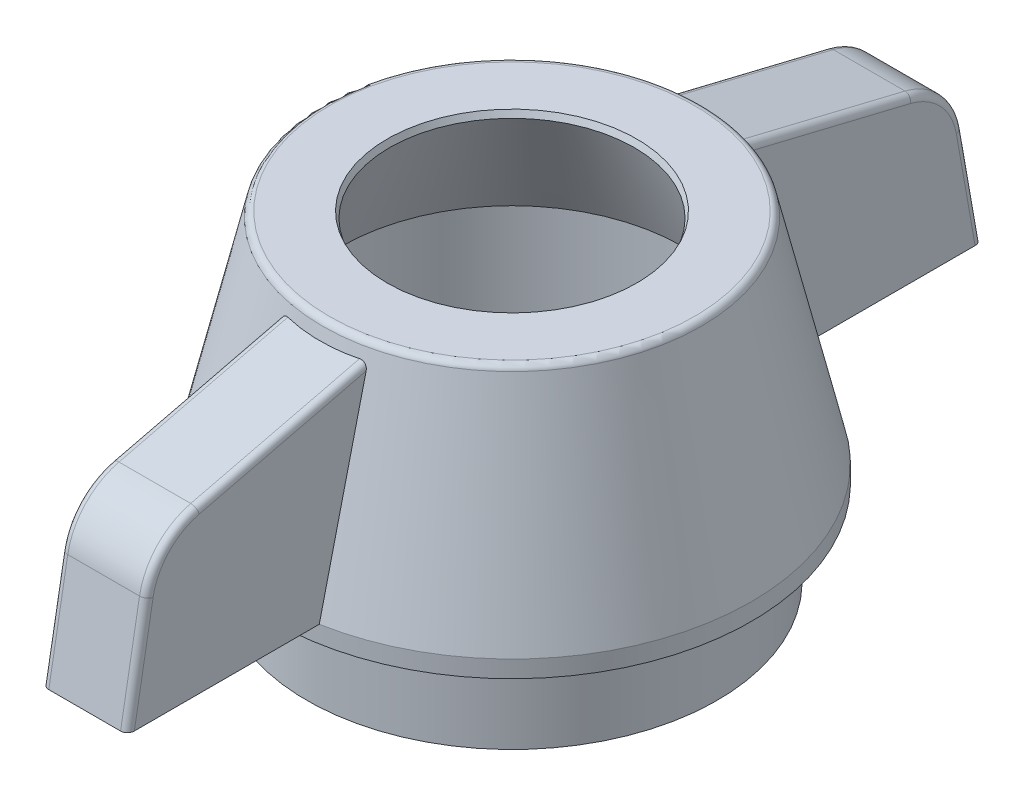
SolidWorks part; units mm, degrees
ref_plane "前视基准面" through (0, 0, 0) normal (0, 0, 1) x (1, 0, 0)
ref_plane "上视基准面" through (0, 0, 0) normal (0, 1, 0) x (1, 0, 0)
ref_plane "右视基准面" through (0, 0, 0) normal (1, 0, 0) x (0, 0, -1)
sketch "草图1" plane through (0, 0, 0) normal (0, 0, 1) x (1, 0, 0)
  line L0 (0, 0) -> (6, 0) construction
  line L1 (6, 0) -> (6, 2.5)
  line L2 (6, 2.5) -> (7, 2.5)
  line L3 (7, 2.5) -> (7, 3)
  line L4 (5.5, 9.4) -> (3.5, 9.4)
  line L5 (3.5, 9.4) -> (5, 6)
  line L6 (5, 6) -> (5, 0)
  line L7 (5, 0) -> (6, 0)
  line L8 (0, 0) -> (0, 9.4) construction
  line L9 (7, 3) -> (5.5, 9.4)
  dimension "D1" = 6
  dimension "D2" = 2.5
  dimension "D3" = 1
  dimension "D4" = 1
  dimension "D5" = 6
  dimension "D6" = 3.5
  dimension "D7" = 9.4
  dimension "D8" = 2
  dimension "D9" = 0.5
revolve "旋转1" add sketch "草图1" angle 360 about L8
sketch "草图2" plane through (0, 0, 0) normal (1, 0, 0) x (0, 0, -1)
  line L0 (-7, 3) -> (-12.5, 3)
  line L1 (-12.5, 3) -> (-11.7186, 7.4316)
  line L2 (-11.7186, 7.4316) -> (-5.6141, 8.9132)
  line L3 (-5.5, 9.4) -> (-7, 3) construction
  line L4 (-5.6141, 8.9132) -> (-5, 9.0622)
  line L5 (-5, 9.0622) -> (-5, 3)
  line L6 (-5, 3) -> (-7, 3)
  dimension "D1" = 5.5
  dimension "D2" = 2
  dimension "D3" = 180
  dimension "D4" = 0.5
  dimension "D5" = 80
  dimension "D6" = 4.5
extrude "凸台-拉伸1" add sketch "草图2" along normal blind 1.25 and the other way blind 1.25
sketch "草图3" plane through (0, 3, 0) normal (0, -1, 0) x (1, 0, 0)
  line L0 (0, 7) -> (0, 7.5) construction
  line L1 (-0.5, 7.5) -> (-0.5, 6.9821)
  line L2 (0.5, 7.5) -> (0.5, 6.9821)
  arc A0 (1.25, 6.8875) -> (-1.25, 6.8875) centre (0, 0) ccw construction
  arc A1 (0.5, 7.5) -> (-0.5, 7.5) centre (0, 7.5) ccw
  arc A2 (-0.5, 6.9821) -> (0.5, 6.9821) centre (0, 0) cw
  dimension "D2" = 0.5
  dimension "D1" = 0.5
extrude "凸台-拉伸2" add sketch "草图3" along normal blind 0.5
fillet "圆角1" radius 2 1 edges at (0, 7.4316, 11.7186)
mirror "镜向1" about plane through (0, 0, 0) normal (0, 0, 1) of "凸台-拉伸1", "凸台-拉伸2", "圆角1"
fillet "圆角2" radius 0.2 13 edges at (-1.25, 4.5719, -12.2228) (-1.25, 7.165, -11.4345) (1.25, 4.5719, -12.2228) (1.25, 7.165, -11.4345) (-1.25, 4.5719, 12.2228) (-1.25, 7.165, 11.4345) (1.25, 4.5719, 12.2228) (1.25, 7.165, 11.4345) (-1.25, 8.3448, -7.9561) (1.25, 8.3448, -7.9561) (-1.25, 8.3448, 7.9561) (1.25, 8.3448, 7.9561) (0, 9.4, -5.5)
chamfer "倒角1" distance 0.2 angle 45 1 edges at (0, 9.4, -3.5) first distance on face at (0, 6, -5)
